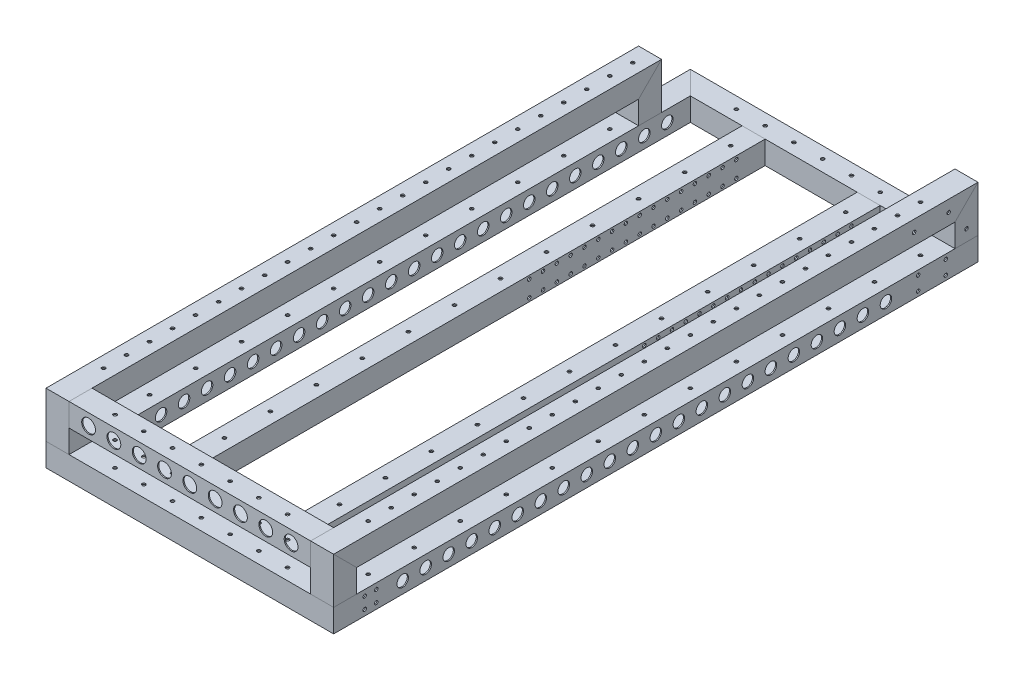
SolidWorks part; units mm, degrees
material "6061 合金"
ref_plane "前视基准面" through (0, 0, 0) normal (0, 0, 1) x (1, 0, 0)
ref_plane "上视基准面" through (0, 0, 0) normal (0, 1, 0) x (1, 0, 0)
ref_plane "右视基准面" through (0, 0, 0) normal (1, 0, 0) x (0, 0, -1)
sketch "草图1" plane through (0, 0, 0) normal (0, 1, 0) x (1, 0, 0)
  line L0 (-50, 270) -> (-50, -270)
  line L1 (-115, -270) -> (115, -270)
  line L2 (-115, -270) -> (-115, 270)
  line L3 (-115, 270) -> (115, 270)
  line L4 (115, -270) -> (115, 270)
  line L5 (-115, -270) -> (115, 270) construction
  line L6 (-115, 270) -> (115, -270) construction
  line L7 (0, -270) -> (0, 270) construction
  line L8 (50, 270) -> (50, -270)
  point P0 (0, 0)
  dimension "D1" = 230
  dimension "D2" = 540
  dimension "D3" = 50
other "Wl 20X20X1(2)" corner treatment miter
ref_plane "基准面2" through (-115, 0, 270) normal (0, 0, -1) x (-1, 0, 0)
sketch "草图12" plane through (-115, 0, 270) normal (0, 0, -1) x (-1, 0, 0)
  line L8 (-9, -9) -> (9, -9)
  line L9 (-10, -10) -> (10, -10)
  line L10 (-10, -10) -> (-10, 10)
  line L11 (-10, 10) -> (10, 10)
  line L12 (10, -10) -> (10, 10)
  line L13 (9, -9) -> (9, 9)
  line L14 (-9, 9) -> (9, 9)
  line L15 (-9, -9) -> (-9, 9)
  point P4 (0, 0)
  dimension "D1" = 20
  dimension "D2" = 20
ref_plane "基准面3" through (115, 0, 0) normal (1, 0, 0) x (0, 0, -1)
ref_plane "基准面4" through (-115, 0, 0) normal (1, 0, 0) x (0, 0, -1)
sketch "草图13" plane through (115, 0, 0) normal (1, 0, 0) x (0, 0, -1)
  line L0 (-280, 10) -> (-260, 10) construction
  line L1 (-270, 10) -> (-270, 40)
  line L2 (260, 10) -> (280, 10) construction
  line L3 (270, 10) -> (270, 40)
  line L4 (270, 40) -> (-270, 40)
  line L6 (-280, 10) -> (280, 10) construction
  dimension "D1" = 30
sketch "草图14" plane through (-115, 0, 0) normal (1, 0, 0) x (0, 0, -1)
  line L1 (270, 40) -> (-270, 40) construction
  line L2 (-270, 10) -> (-270, 40) construction
  line L3 (225, 10) -> (225, 40)
  line L4 (225, 40) -> (-270, 40)
  line L5 (-270, 10) -> (-270, 40)
  line L6 (280, -10) -> (280, 10) construction
  dimension "D1" = 55
other "Wl 20X20X1(4)" corner treatment miter
ref_plane "基准面5" through (-115, 10, 270) normal (0, 1, 0) x (0, 0, 1)
sketch "草图15" plane through (-115, 10, 270) normal (0, 1, 0) x (0, 0, 1)
  line L8 (-9, -9) -> (9, -9)
  line L9 (-10, -10) -> (10, -10)
  line L10 (-10, -10) -> (-10, 10)
  line L11 (-10, 10) -> (10, 10)
  line L12 (10, -10) -> (10, 10)
  line L13 (9, -9) -> (9, 9)
  line L14 (-9, 9) -> (9, 9)
  line L15 (-9, -9) -> (-9, 9)
  point P4 (0, 0)
  dimension "D1" = 20
  dimension "D2" = 20
ref_plane "基准面6" through (0, 40, 0) normal (0, 1, 0) x (1, 0, 0)
sketch "草图16" plane through (0, 40, 0) normal (0, 1, 0) x (1, 0, 0)
  line L0 (-105, -270) -> (105, -270)
  line L1 (-115, -270) -> (115, -270) construction
  line L2 (-105, 235) -> (-105, -280) construction
  line L3 (105, 280) -> (105, -280) construction
other "Wl 20X20X1(5)" corner treatment miter
ref_plane "基准面7" through (-105, 40, 270) normal (1, 0, 0) x (0, 0, -1)
sketch "草图17" plane through (-105, 40, 270) normal (1, 0, 0) x (0, 0, -1)
  line L8 (-9, -9) -> (9, -9)
  line L9 (-10, -10) -> (10, -10)
  line L10 (-10, -10) -> (-10, 10)
  line L11 (-10, 10) -> (10, 10)
  line L12 (10, -10) -> (10, 10)
  line L13 (9, -9) -> (9, 9)
  line L14 (-9, 9) -> (9, 9)
  line L15 (-9, -9) -> (-9, 9)
  point P4 (0, 0)
  dimension "D1" = 20
  dimension "D2" = 20
sketch "草图18" plane through (0, 50, 0) normal (0, 1, 0) x (1, 0, 0)
  line L0 (115, -280) -> (115, 280) construction
  line L1 (125, -280) -> (105, -280) construction
  line L2 (115, 260) -> (115, 280) construction
  line L3 (105, -260) -> (-105, -260) construction
  line L4 (0, 280) -> (0, -280) construction
  line L5 (125, 280) -> (-125, 280) construction
  line L6 (105, -280) -> (-105, -280) construction
  line L7 (-115, -280) -> (-115, 280) construction
  circle A0 centre (115, -240) radius 1.5
  circle A1 centre (115, -220) radius 1.5
  circle A2 centre (115, -200) radius 1.5
  circle A3 centre (115, -180) radius 1.5
  circle A4 centre (115, -160) radius 1.5
  circle A5 centre (115, -140) radius 1.5
  circle A6 centre (115, -120) radius 1.5
  circle A7 centre (115, -100) radius 1.5
  circle A8 centre (115, -80) radius 1.5
  circle A9 centre (115, -60) radius 1.5
  circle A10 centre (115, -40) radius 1.5
  circle A11 centre (115, -20) radius 1.5
  circle A12 centre (115, 0) radius 1.5
  circle A13 centre (115, 20) radius 1.5
  circle A14 centre (115, 40) radius 1.5
  circle A15 centre (115, 60) radius 1.5
  circle A16 centre (115, 80) radius 1.5
  circle A17 centre (115, 100) radius 1.5
  circle A18 centre (115, 120) radius 1.5
  circle A19 centre (115, 140) radius 1.5
  circle A20 centre (115, 160) radius 1.5
  circle A21 centre (115, 180) radius 1.5
  circle A22 centre (115, 200) radius 1.5
  circle A23 centre (115, 220) radius 1.5
  circle A24 centre (115, 240) radius 1.5
  circle A25 centre (-115, 240) radius 1.5
  circle A26 centre (-115, 220) radius 1.5
  circle A27 centre (-115, 200) radius 1.5
  circle A28 centre (-115, 180) radius 1.5
  circle A29 centre (-115, 160) radius 1.5
  circle A30 centre (-115, 140) radius 1.5
  circle A31 centre (-115, 120) radius 1.5
  circle A32 centre (-115, 100) radius 1.5
  circle A33 centre (-115, 80) radius 1.5
  circle A34 centre (-115, 60) radius 1.5
  circle A35 centre (-115, 40) radius 1.5
  circle A36 centre (-115, 20) radius 1.5
  circle A37 centre (-115, 0) radius 1.5
  circle A38 centre (-115, -20) radius 1.5
  circle A39 centre (-115, -40) radius 1.5
  circle A40 centre (-115, -60) radius 1.5
  circle A41 centre (-115, -80) radius 1.5
  circle A42 centre (-115, -100) radius 1.5
  circle A43 centre (-115, -120) radius 1.5
  circle A44 centre (-115, -140) radius 1.5
  circle A45 centre (-115, -160) radius 1.5
  circle A46 centre (-115, -180) radius 1.5
  circle A47 centre (-115, -200) radius 1.5
  circle A48 centre (-115, -220) radius 1.5
  circle A49 centre (-115, -240) radius 1.5
  dimension "D1" = 3
  dimension "D2" = 20
  dimension "D3" = 25
extrude "切除-拉伸1" cut sketch "草图18" against normal blind 20
sketch "草图19" plane through (125, 0, 0) normal (1, 0, 0) x (0, 0, -1)
  line L0 (-280, 0) -> (280, 0) construction
  line L1 (-280, -10) -> (-280, 10) construction
  line L2 (280, 10) -> (280, -10) construction
  line L4 (-253, -5) -> (-243, -5) construction
  line L5 (-253, -5) -> (-253, 5) construction
  line L6 (-253, 5) -> (-243, 5) construction
  line L7 (-243, -5) -> (-243, 5) construction
  line L8 (-253, -5) -> (-243, 5) construction
  line L9 (-253, 5) -> (-243, -5) construction
  circle A0 centre (-253, 5) radius 1.5
  circle A1 centre (-243, 5) radius 1.5
  circle A2 centre (-243, -5) radius 1.5
  circle A3 centre (-253, -5) radius 1.5
  point P6 (-248, 0)
  dimension "D1" = 3
  dimension "D2" = 3
  dimension "D3" = 10
  dimension "D4" = 10
  dimension "D5" = 27
extrude "切除-拉伸2" cut sketch "草图19" against normal blind 20
sketch "草图20" plane through (-125, 0, 0) normal (-1, 0, 0) x (0, 0, 1)
  line L0 (280, 0) -> (-280, 0) construction
  line L1 (280, 10) -> (280, -10) construction
  line L2 (-280, -10) -> (-280, 10) construction
  line L4 (243, -5) -> (253, -5) construction
  line L5 (243, -5) -> (243, 5) construction
  line L6 (243, 5) -> (253, 5) construction
  line L7 (253, -5) -> (253, 5) construction
  line L8 (243, -5) -> (253, 5) construction
  line L9 (243, 5) -> (253, -5) construction
  circle A0 centre (243, 5) radius 1.5
  circle A1 centre (253, 5) radius 1.5
  circle A2 centre (243, -5) radius 1.5
  circle A3 centre (253, -5) radius 1.5
  point P6 (248, 0)
  dimension "D4" = 3
  dimension "D5" = 3
  dimension "D1" = 10
  dimension "D2" = 10
  dimension "D3" = 27
extrude "切除-拉伸3" cut sketch "草图20" against normal blind 20
sketch "草图21" plane through (60, 0, 0) normal (1, 0, 0) x (0, 0, -1)
  line L0 (151, -7) -> (163, -7) construction
  line L1 (280, 10) -> (280, -10) construction
  line L2 (199, -7) -> (211, -7) construction
  line L3 (151, -7) -> (151, 7) construction
  line L4 (175, -7) -> (187, -7) construction
  line L5 (175, -7) -> (175, 7) construction
  line L6 (175, 7) -> (187, 7) construction
  line L7 (187, -7) -> (187, 7) construction
  line L8 (175, -7) -> (187, 7) construction
  line L9 (175, 7) -> (187, -7) construction
  line L10 (151, 7) -> (163, 7) construction
  line L11 (163, -7) -> (163, 7) construction
  line L12 (151, -7) -> (163, 7) construction
  line L13 (151, 7) -> (163, -7) construction
  line L14 (127, -7) -> (139, -7) construction
  line L15 (127, -7) -> (127, 7) construction
  line L16 (127, 7) -> (139, 7) construction
  line L17 (139, -7) -> (139, 7) construction
  line L18 (127, -7) -> (139, 7) construction
  line L19 (127, 7) -> (139, -7) construction
  line L20 (103, -7) -> (115, -7) construction
  line L21 (103, -7) -> (103, 7) construction
  line L22 (103, 7) -> (115, 7) construction
  line L23 (115, -7) -> (115, 7) construction
  line L24 (103, -7) -> (115, 7) construction
  line L25 (103, 7) -> (115, -7) construction
  line L26 (79, -7) -> (91, -7) construction
  line L27 (79, -7) -> (79, 7) construction
  line L28 (79, 7) -> (91, 7) construction
  line L29 (91, -7) -> (91, 7) construction
  line L30 (79, -7) -> (91, 7) construction
  line L31 (79, 7) -> (91, -7) construction
  line L32 (55, -7) -> (67, -7) construction
  line L33 (55, -7) -> (55, 7) construction
  line L34 (55, 7) -> (67, 7) construction
  line L35 (67, -7) -> (67, 7) construction
  line L36 (55, -7) -> (67, 7) construction
  line L37 (55, 7) -> (67, -7) construction
  line L38 (-280, 10) -> (280, 10) construction
  line L39 (199, -7) -> (199, 7) construction
  line L40 (199, 7) -> (211, 7) construction
  line L41 (211, -7) -> (211, 7) construction
  line L42 (199, -7) -> (211, 7) construction
  line L43 (199, 7) -> (211, -7) construction
  line L44 (223, -7) -> (235, -7) construction
  line L45 (223, -7) -> (223, 7) construction
  line L46 (223, 7) -> (235, 7) construction
  line L47 (235, -7) -> (235, 7) construction
  line L48 (223, -7) -> (235, 7) construction
  line L49 (223, 7) -> (235, -7) construction
  circle A0 centre (175, 7) radius 1.5
  circle A1 centre (187, 7) radius 1.5
  circle A2 centre (175, -7) radius 1.5
  circle A3 centre (187, -7) radius 1.5
  circle A20 centre (151, 7) radius 1.5
  circle A21 centre (163, 7) radius 1.5
  circle A22 centre (151, -7) radius 1.5
  circle A23 centre (163, -7) radius 1.5
  circle A24 centre (127, 7) radius 1.5
  circle A25 centre (139, 7) radius 1.5
  circle A26 centre (127, -7) radius 1.5
  circle A27 centre (139, -7) radius 1.5
  circle A28 centre (103, 7) radius 1.5
  circle A29 centre (115, 7) radius 1.5
  circle A30 centre (103, -7) radius 1.5
  circle A31 centre (115, -7) radius 1.5
  circle A32 centre (79, 7) radius 1.5
  circle A33 centre (91, 7) radius 1.5
  circle A34 centre (79, -7) radius 1.5
  circle A35 centre (91, -7) radius 1.5
  circle A36 centre (55, 7) radius 1.5
  circle A37 centre (67, 7) radius 1.5
  circle A38 centre (55, -7) radius 1.5
  circle A39 centre (67, -7) radius 1.5
  circle A40 centre (199, 7) radius 1.5
  circle A41 centre (211, 7) radius 1.5
  circle A42 centre (199, -7) radius 1.5
  circle A43 centre (211, -7) radius 1.5
  circle A44 centre (223, 7) radius 1.5
  circle A45 centre (235, 7) radius 1.5
  circle A46 centre (223, -7) radius 1.5
  circle A47 centre (235, -7) radius 1.5
  point P4 (157, 0)
  point P6 (181, 0)
  point P22 (133, 0)
  point P31 (109, 0)
  point P40 (85, 0)
  point P49 (61, 0)
  point P60 (205, 0)
  point P69 (229, 0)
  dimension "D4" = 3
  dimension "D5" = 3
  dimension "D1" = 14
  dimension "D2" = 12
  dimension "D3" = 93
  dimension "D7" = 12
  dimension "D8" = 10
  dimension "D6" = 6
extrude "切除-拉伸4" cut sketch "草图21" against normal blind 120
sketch "草图22" plane through (125, 0, 0) normal (1, 0, 0) x (0, 0, -1)
  line L0 (0, -10) -> (0, 10.6802) construction
  line L1 (-280, -10) -> (280, -10) construction
  circle A0 centre (0, 0) radius 5
  circle A1 centre (20, 0) radius 5
  circle A2 centre (40, 0) radius 5
  circle A3 centre (60, 0) radius 5
  circle A4 centre (80, 0) radius 5
  circle A5 centre (100, 0) radius 5
  circle A6 centre (120, 0) radius 5
  circle A7 centre (140, 0) radius 5
  circle A8 centre (160, 0) radius 5
  circle A9 centre (180, 0) radius 5
  circle A10 centre (200, 0) radius 5
  circle A11 centre (220, 0) radius 5 construction
  circle A12 centre (240, 0) radius 5 construction
  circle A13 centre (-240, 0) radius 5 construction
  circle A14 centre (-220, 0) radius 5
  circle A15 centre (-200, 0) radius 5
  circle A16 centre (-180, 0) radius 5
  circle A17 centre (-160, 0) radius 5
  circle A18 centre (-140, 0) radius 5
  circle A19 centre (-120, 0) radius 5
  circle A20 centre (-100, 0) radius 5
  circle A21 centre (-80, 0) radius 5
  circle A22 centre (-60, 0) radius 5
  circle A23 centre (-40, 0) radius 5
  circle A24 centre (-20, 0) radius 5
  dimension "D1" = 10
  dimension "D2" = 13
extrude "切除-拉伸5" cut sketch "草图22" against normal blind 20
sketch "草图23" plane through (-125, 0, 0) normal (-1, 0, 0) x (0, 0, 1)
  line L0 (0, -10) -> (0, 10) construction
  line L1 (-280, 0) -> (280, 0) construction
  line L2 (-280, -10) -> (-280, 10) construction
  line L3 (280, 10) -> (280, -10) construction
  line L4 (-280, -10) -> (280, -10) construction
  line L5 (-280, 10) -> (280, 10) construction
  circle A0 centre (0, 0) radius 5
  circle A1 centre (-20, 0) radius 5
  circle A2 centre (-40, 0) radius 5
  circle A3 centre (-60, 0) radius 5
  circle A4 centre (-80, 0) radius 5
  circle A5 centre (-100, 0) radius 5
  circle A6 centre (-120, 0) radius 5
  circle A7 centre (-140, 0) radius 5
  circle A8 centre (-160, 0) radius 5
  circle A9 centre (-180, 0) radius 5
  circle A10 centre (-200, 0) radius 5
  circle A11 centre (-220, 0) radius 5
  circle A12 centre (-240, 0) radius 5
  circle A13 centre (240, 0) radius 5 construction
  circle A14 centre (220, 0) radius 5
  circle A15 centre (200, 0) radius 5
  circle A16 centre (180, 0) radius 5
  circle A17 centre (160, 0) radius 5
  circle A18 centre (140, 0) radius 5
  circle A19 centre (120, 0) radius 5
  circle A20 centre (100, 0) radius 5
  circle A21 centre (80, 0) radius 5
  circle A22 centre (60, 0) radius 5
  circle A23 centre (40, 0) radius 5
  circle A24 centre (20, 0) radius 5
  dimension "D1" = 10
extrude "切除-拉伸6" cut sketch "草图23" against normal blind 20
sketch "草图24" plane through (0, 0, 280) normal (0, 0, 1) x (1, 0, 0)
  line L0 (-105, 40) -> (105, 40) construction
  line L1 (-105, 40) -> (105, 40) construction
  line L2 (11, 40) -> (-11, 40) construction
  line L3 (0, 40) -> (0, 50) construction
  line L4 (105, 50) -> (-105, 50) construction
  circle A0 centre (0, 40) radius 6
  circle A1 centre (22, 40) radius 6
  circle A2 centre (44, 40) radius 6
  circle A3 centre (66, 40) radius 6
  circle A4 centre (88, 40) radius 6
  circle A5 centre (-88, 40) radius 6
  circle A6 centre (-66, 40) radius 6
  circle A7 centre (-44, 40) radius 6
  circle A8 centre (-22, 40) radius 6
  dimension "D1" = 12
  dimension "D2" = 5
extrude "切除-拉伸7" cut sketch "草图24" against normal blind 20
sketch "草图25" plane through (125, 0, 0) normal (1, 0, 0) x (0, 0, -1)
  line L0 (270, 40) -> (183.2761, 40) construction
  line L1 (270, 40) -> (-270, 40) construction
  line L2 (280, 10) -> (280, 50) construction
  line L3 (270, 10) -> (270, 40) construction
  circle A0 centre (254.5, 40) radius 1.5
  circle A1 centre (270, 20) radius 1.5
  circle A3 centre (224.5, 40) radius 1.5
  dimension "D1" = 3
  dimension "D2" = 25.5
  dimension "D3" = 3
  dimension "D4" = 3
  dimension "D5" = 30
extrude "切除-拉伸8" cut sketch "草图25" against normal blind 20
sketch "草图27" plane through (125, 0, 0) normal (1, 0, 0) x (0, 0, -1)
  line L0 (280, 0) -> (211.5758, 0) construction
  line L1 (280, 10) -> (280, -10) construction
  line L2 (-270, 0) -> (270, 0) construction
  line L4 (228, -6) -> (252, -6) construction
  line L5 (228, -6) -> (228, 6) construction
  line L6 (228, 6) -> (252, 6) construction
  line L7 (252, -6) -> (252, 6) construction
  line L8 (228, -6) -> (252, 6) construction
  line L9 (228, 6) -> (252, -6) construction
  circle A0 centre (252, 6) radius 1.5
  circle A1 centre (228, 6) radius 1.5
  circle A2 centre (228, -6) radius 1.5
  circle A3 centre (252, -6) radius 1.5
  point P6 (240, 0)
  dimension "D1" = 3
  dimension "D2" = 3
  dimension "D3" = 24
  dimension "D4" = 12
  dimension "D5" = 28
extrude "切除-拉伸9" cut sketch "草图27" against normal blind 20
sketch "草图28" plane through (0, 50, 0) normal (0, 1, 0) x (1, 0, 0)
  line L0 (-105, -270) -> (105, -270) construction
  line L1 (0, -280) -> (0, -260) construction
  line L2 (0, -270) -> (0, 270) construction
  line L3 (105, -280) -> (-105, -280) construction
  line L4 (105, -260) -> (-105, -260) construction
  circle A0 centre (0, -270) radius 1.5
  circle A1 centre (25, -270) radius 1.5
  circle A2 centre (50, -270) radius 1.5
  circle A3 centre (75, -270) radius 1.5
  circle A4 centre (-75, -270) radius 1.5
  circle A5 centre (-50, -270) radius 1.5
  circle A6 centre (-25, -270) radius 1.5
  point P24 (0, -260)
  dimension "D1" = 3
  dimension "D2" = 4
extrude "切除-拉伸10" cut sketch "草图28" against normal through all
sketch "草图29" plane through (0, -10, 0) normal (0, -1, 0) x (1, 0, 0)
  line L0 (50, -260) -> (50, 260) construction
  line L1 (60, -260) -> (40, -260) construction
  line L2 (40, 260) -> (60, 260) construction
  line L3 (0, 260) -> (0, -260) construction
  line L4 (-105, 260) -> (105, 260) construction
  line L5 (0, 270) -> (0, -270) construction
  line L6 (-126.2598, 0) -> (125, 0) construction
  line L7 (125, 280) -> (125, -280) construction
  line L8 (60, -260) -> (105, -260) construction
  line L9 (105, -260) -> (-105, -260) construction
  line L10 (60, 260) -> (60, -260) construction
  line L11 (82.5, -260) -> (82.5, 260) construction
  line L12 (126.2598, 0) -> (-125, 0) construction
  circle A1 centre (50, 0) radius 1.5
  circle A2 centre (50, 40) radius 1.5
  circle A3 centre (50, 80) radius 1.5
  circle A4 centre (50, 120) radius 1.5
  circle A5 centre (50, 160) radius 1.5
  circle A6 centre (50, 200) radius 1.5
  circle A7 centre (50, 240) radius 1.5
  circle A8 centre (50, -240) radius 1.5
  circle A9 centre (50, -200) radius 1.5
  circle A10 centre (50, -160) radius 1.5
  circle A11 centre (50, -120) radius 1.5
  circle A12 centre (50, -80) radius 1.5
  circle A13 centre (50, -40) radius 1.5
  circle A14 centre (-50, -40) radius 1.5
  circle A15 centre (-50, -80) radius 1.5
  circle A16 centre (-50, -120) radius 1.5
  circle A17 centre (-50, -160) radius 1.5
  circle A18 centre (-50, -200) radius 1.5
  circle A19 centre (-50, -240) radius 1.5
  circle A20 centre (-50, 240) radius 1.5
  circle A21 centre (-50, 200) radius 1.5
  circle A22 centre (-50, 160) radius 1.5
  circle A23 centre (-50, 120) radius 1.5
  circle A24 centre (-50, 80) radius 1.5
  circle A25 centre (-50, 40) radius 1.5
  circle A26 centre (-50, 0) radius 1.5
  circle A27 centre (75, 270) radius 1.5 construction
  circle A28 centre (50, 270) radius 1.5 construction
  circle A29 centre (25, 270) radius 1.5 construction
  circle A30 centre (0, 270) radius 1.5 construction
  circle A31 centre (-25, 270) radius 1.5 construction
  circle A32 centre (-50, 270) radius 1.5 construction
  circle A33 centre (-75, 270) radius 1.5 construction
  circle A34 centre (75, 270) radius 1.5
  circle A35 centre (50, 270) radius 1.5
  circle A36 centre (25, 270) radius 1.5
  circle A37 centre (0, 270) radius 1.5
  circle A38 centre (-25, 270) radius 1.5
  circle A39 centre (-50, 270) radius 1.5
  circle A40 centre (-75, 270) radius 1.5
  circle A41 centre (-75, -270) radius 1.5
  circle A42 centre (-50, -270) radius 1.5
  circle A43 centre (-25, -270) radius 1.5
  circle A44 centre (0, -270) radius 1.5
  circle A45 centre (25, -270) radius 1.5
  circle A46 centre (50, -270) radius 1.5
  circle A47 centre (75, -270) radius 1.5
  circle A48 centre (115, -40) radius 1.5
  circle A49 centre (115, -80) radius 1.5
  circle A50 centre (115, -120) radius 1.5
  circle A51 centre (115, -160) radius 1.5
  circle A52 centre (115, -200) radius 1.5
  circle A53 centre (115, -240) radius 1.5
  circle A54 centre (115, 240) radius 1.5
  circle A55 centre (115, 200) radius 1.5
  circle A56 centre (115, 160) radius 1.5
  circle A57 centre (115, 120) radius 1.5
  circle A58 centre (115, 80) radius 1.5
  circle A59 centre (115, 40) radius 1.5
  circle A60 centre (115, 0) radius 1.5
  circle A61 centre (-115, 0) radius 1.5
  circle A62 centre (-115, 40) radius 1.5
  circle A63 centre (-115, 80) radius 1.5
  circle A64 centre (-115, 120) radius 1.5
  circle A65 centre (-115, 160) radius 1.5
  circle A66 centre (-115, 200) radius 1.5
  circle A67 centre (-115, 240) radius 1.5
  circle A68 centre (-115, -240) radius 1.5
  circle A69 centre (-115, -200) radius 1.5
  circle A70 centre (-115, -160) radius 1.5
  circle A71 centre (-115, -120) radius 1.5
  circle A72 centre (-115, -80) radius 1.5
  circle A73 centre (-115, -40) radius 1.5
  dimension "D1" = 3
  dimension "D2" = 7
extrude "切除-拉伸11" cut sketch "草图29" against normal blind 20
sketch "草图30" plane through (0, 50, 0) normal (0, 1, 0) x (1, 0, 0)
  line L0 (0, -280) -> (0, 280) construction
  line L1 (105, -280) -> (-105, -280) construction
  line L2 (125, 280) -> (-125, 280) construction
  line L3 (125, 280) -> (125, -280) construction
  line L4 (105, -280) -> (125, -280) construction
  line L5 (-125, -280) -> (-105, -280) construction
  line L6 (-125, 235) -> (-125, -280) construction
  line L7 (125, 280) -> (125, -280)
  line L8 (105, -280) -> (125, -280)
  line L9 (105, -280) -> (-105, -280)
  line L10 (-125, -280) -> (-105, -280)
  line L11 (-125, 235) -> (-125, -280)
  circle A0 centre (-115, -240) radius 1.5 construction
  circle A1 centre (-115, -240) radius 1.5
  circle A2 centre (-115, -220) radius 1.5
  circle A3 centre (-115, -200) radius 1.5
  circle A4 centre (-115, -180) radius 1.5
  circle A5 centre (-115, -160) radius 1.5
  circle A6 centre (-115, -140) radius 1.5
  circle A7 centre (-115, -120) radius 1.5
  circle A8 centre (-115, -100) radius 1.5
  circle A9 centre (-115, -80) radius 1.5
  circle A10 centre (-115, -60) radius 1.5
  circle A11 centre (-115, -40) radius 1.5
  circle A12 centre (-115, -20) radius 1.5
  circle A13 centre (-115, 0) radius 1.5
  circle A14 centre (-115, 20) radius 1.5
  circle A15 centre (-115, 40) radius 1.5
  circle A16 centre (-115, 60) radius 1.5
  circle A17 centre (-115, 80) radius 1.5
  circle A18 centre (-115, 100) radius 1.5
  circle A19 centre (-115, 120) radius 1.5
  circle A20 centre (-115, 140) radius 1.5
  circle A21 centre (-115, 160) radius 1.5
  circle A22 centre (-115, 180) radius 1.5
  circle A23 centre (-115, 200) radius 1.5
  circle A24 centre (115, -240) radius 1.5 construction
  circle A25 centre (115, -240) radius 1.5
  circle A26 centre (115, -220) radius 1.5
  circle A27 centre (115, -200) radius 1.5
  circle A28 centre (115, -180) radius 1.5
  circle A29 centre (115, -160) radius 1.5
  circle A30 centre (115, -140) radius 1.5
  circle A31 centre (115, -120) radius 1.5
  circle A32 centre (115, -100) radius 1.5
  circle A33 centre (115, -80) radius 1.5
  circle A34 centre (115, -60) radius 1.5
  circle A35 centre (115, -40) radius 1.5
  circle A36 centre (115, -20) radius 1.5
  circle A37 centre (115, 0) radius 1.5
  circle A38 centre (115, 20) radius 1.5
  circle A39 centre (115, 40) radius 1.5
  circle A40 centre (115, 60) radius 1.5
  circle A41 centre (115, 80) radius 1.5
  circle A42 centre (115, 100) radius 1.5
  circle A43 centre (115, 120) radius 1.5
  circle A44 centre (115, 140) radius 1.5
  circle A45 centre (115, 160) radius 1.5
  circle A46 centre (115, 180) radius 1.5
  circle A47 centre (115, 200) radius 1.5
  circle A48 centre (115, 220) radius 1.5
  circle A49 centre (115, 240) radius 1.5
  circle A54 centre (-75, -270) radius 1.5 construction
  circle A55 centre (-50, -270) radius 1.5 construction
  circle A56 centre (-25, -270) radius 1.5 construction
  circle A57 centre (75, -270) radius 1.5 construction
  circle A58 centre (50, -270) radius 1.5 construction
  circle A59 centre (25, -270) radius 1.5 construction
  circle A60 centre (0, -270) radius 1.5 construction
  circle A61 centre (75, -270) radius 1.5
  circle A62 centre (50, -270) radius 1.5
  circle A63 centre (25, -270) radius 1.5
  circle A64 centre (0, -270) radius 1.5
  circle A65 centre (-25, -270) radius 1.5
  circle A66 centre (-50, -270) radius 1.5
  circle A67 centre (-75, -270) radius 1.5
  dimension "D1" = 23
  dimension "D2" = 25
sketch "草图31" plane through (0, -10, 0) normal (0, -1, 0) x (1, 0, 0)
  line L0 (0, 0) -> (125, 0) construction
  line L1 (-115, -270) -> (115, 270) construction
  line L2 (125, 280) -> (125, -280) construction
  line L3 (125, -280) -> (-125, -280) construction
  line L4 (-125, 280) -> (125, 280) construction
  line L5 (-125, -280) -> (-125, 280) construction
  line L6 (125, -280) -> (-125, -280)
  line L7 (125, 280) -> (125, -280)
  line L8 (-125, 280) -> (125, 280)
  line L9 (-125, -280) -> (-125, 280)
  circle A0 centre (-115, -240) radius 1.5 construction
  circle A1 centre (-115, -240) radius 1.5
  circle A2 centre (-115, -200) radius 1.5
  circle A3 centre (-115, -160) radius 1.5
  circle A4 centre (-115, -120) radius 1.5
  circle A5 centre (-115, -80) radius 1.5
  circle A6 centre (-115, -40) radius 1.5
  circle A7 centre (-115, 0) radius 1.5
  circle A8 centre (-115, 40) radius 1.5
  circle A9 centre (-115, 80) radius 1.5
  circle A10 centre (-115, 120) radius 1.5
  circle A11 centre (-115, 160) radius 1.5
  circle A12 centre (-115, 200) radius 1.5
  circle A13 centre (-115, 240) radius 1.5
  circle A14 centre (115, -240) radius 1.5 construction
  circle A15 centre (50, -240) radius 1.5 construction
  circle A16 centre (-50, -240) radius 1.5 construction
  circle A17 centre (115, -240) radius 1.5
  circle A18 centre (50, -240) radius 1.5
  circle A19 centre (-50, -240) radius 1.5
  circle A20 centre (115, -200) radius 1.5
  circle A21 centre (50, -200) radius 1.5
  circle A22 centre (-50, -200) radius 1.5
  circle A23 centre (115, -160) radius 1.5
  circle A24 centre (50, -160) radius 1.5
  circle A25 centre (-50, -160) radius 1.5
  circle A26 centre (115, -120) radius 1.5
  circle A27 centre (50, -120) radius 1.5
  circle A28 centre (-50, -120) radius 1.5
  circle A29 centre (115, -80) radius 1.5
  circle A30 centre (50, -80) radius 1.5
  circle A31 centre (-50, -80) radius 1.5
  circle A32 centre (115, -40) radius 1.5
  circle A33 centre (50, -40) radius 1.5
  circle A34 centre (-50, -40) radius 1.5
  circle A35 centre (115, 0) radius 1.5
  circle A36 centre (50, 0) radius 1.5
  circle A37 centre (-50, 0) radius 1.5
  circle A38 centre (115, 40) radius 1.5
  circle A39 centre (50, 40) radius 1.5
  circle A40 centre (-50, 40) radius 1.5
  circle A41 centre (115, 80) radius 1.5
  circle A42 centre (50, 80) radius 1.5
  circle A43 centre (-50, 80) radius 1.5
  circle A44 centre (115, 120) radius 1.5
  circle A45 centre (50, 120) radius 1.5
  circle A46 centre (-50, 120) radius 1.5
  circle A47 centre (115, 160) radius 1.5
  circle A48 centre (50, 160) radius 1.5
  circle A49 centre (-50, 160) radius 1.5
  circle A50 centre (115, 200) radius 1.5
  circle A51 centre (50, 200) radius 1.5
  circle A52 centre (-50, 200) radius 1.5
  circle A53 centre (115, 240) radius 1.5
  circle A54 centre (50, 240) radius 1.5
  circle A55 centre (-50, 240) radius 1.5
  circle A56 centre (75, -270) radius 1.5 construction
  circle A57 centre (50, -270) radius 1.5 construction
  circle A58 centre (25, -270) radius 1.5 construction
  circle A59 centre (0, -270) radius 1.5 construction
  circle A60 centre (-25, -270) radius 1.5 construction
  circle A61 centre (-50, -270) radius 1.5 construction
  circle A62 centre (-75, -270) radius 1.5 construction
  circle A63 centre (75, -270) radius 1.5
  circle A64 centre (50, -270) radius 1.5
  circle A65 centre (25, -270) radius 1.5
  circle A66 centre (0, -270) radius 1.5
  circle A67 centre (-25, -270) radius 1.5
  circle A68 centre (-50, -270) radius 1.5
  circle A69 centre (-75, -270) radius 1.5
  circle A70 centre (-75, 270) radius 1.5
  circle A71 centre (-50, 270) radius 1.5
  circle A72 centre (-25, 270) radius 1.5
  circle A73 centre (0, 270) radius 1.5
  circle A74 centre (25, 270) radius 1.5
  circle A75 centre (50, 270) radius 1.5
  circle A76 centre (75, 270) radius 1.5
  dimension "D1" = 13
  dimension "D2" = 13
